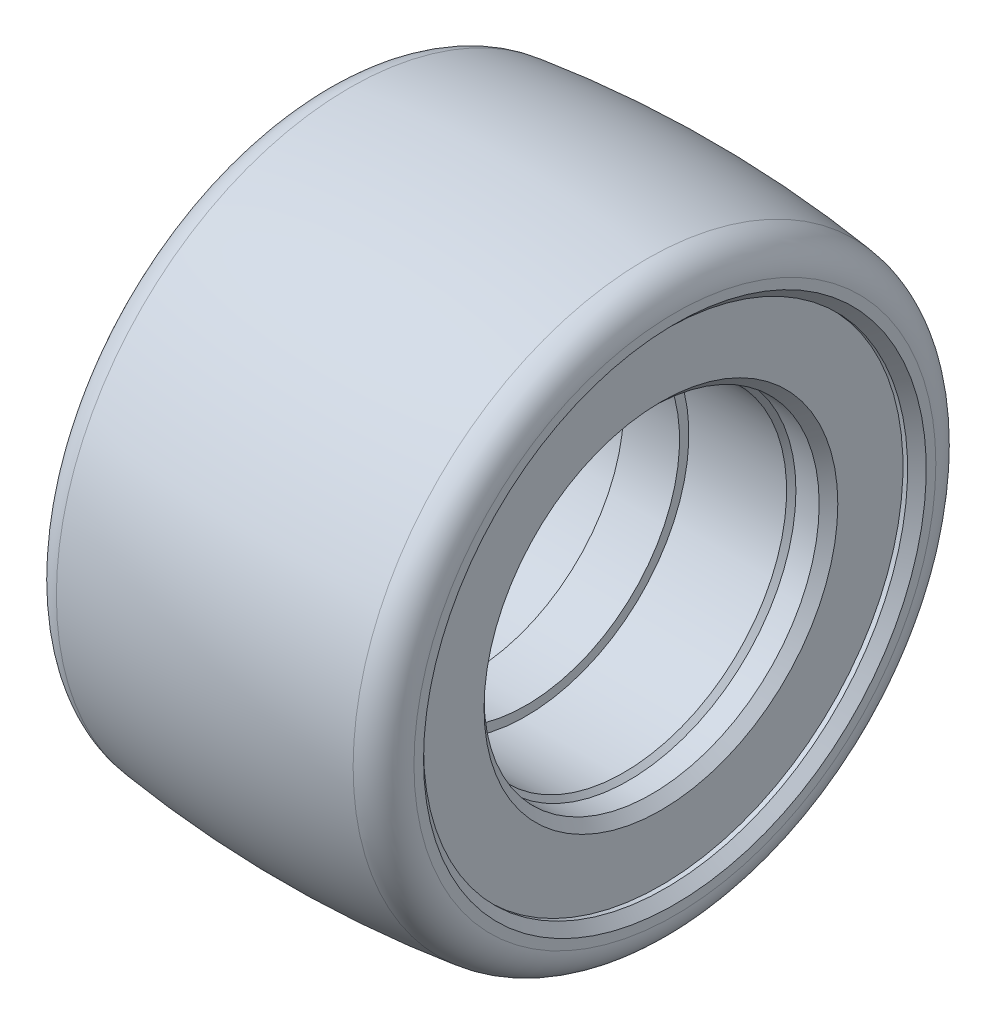
SolidWorks part; units mm, degrees
ref_plane "Front Plane" through (0, 0, 0) normal (0, 0, 1) x (1, 0, 0)
ref_plane "Top Plane" through (0, 0, 0) normal (0, 1, 0) x (1, 0, 0)
ref_plane "Right Plane" through (0, 0, 0) normal (1, 0, 0) x (0, 0, -1)
ref_axis "Axis_X" through (-17.6, 0, 0) along (1, 0, 0)
ref_axis "Axis_Y" through (0, 41.25, 0) along (0, -1, 0)
ref_axis "Axis_Z" through (0, 0, -41.25) along (0, 0, 1)
sketch "Sketch1" plane through (0, 0, 0) normal (0, 0, 1) x (1, 0, 0)
  line L0 (-14, 0) -> (14, 0) construction
  line L2 (-14, 17.5) -> (-3, 17.5)
  line L4 (-19, 32.5) -> (19, 32.5)
  line L5 (0, 0) -> (0, 32.5) construction
  line L8 (-14, 0) -> (14, 0) construction
  line L9 (-3, 17.5) -> (-3, 16.5)
  line L10 (-3, 16.5) -> (3, 16.5)
  line L11 (3, 16.5) -> (3, 17.5)
  line L12 (14, 17.5) -> (14, 18)
  line L13 (14, 18) -> (17.5, 18)
  line L14 (-14, 17.5) -> (-14, 18)
  line L15 (-19, 26) -> (-19, 32.5)
  line L16 (19, 26) -> (19, 32.5)
  line L17 (-14, 18) -> (-17.5, 18)
  line L18 (17.5, 18) -> (17.5, 26)
  line L19 (17.5, 26) -> (19, 26)
  line L20 (3, 17.5) -> (14, 17.5)
  line L21 (-17.5, 18) -> (-17.5, 26)
  line L22 (-17.5, 26) -> (-19, 26)
  dimension "B" = 38
  dimension "D" = 65
  dimension "FIX_1" = 1.5
  dimension "FIX_2" = 1
  dimension "FIX_3" = 1.5
  dimension "FIX_4" = 6
  dimension "FIX_5" = 33
  dimension "FIX_6" = 52
  dimension "FIX_7" = 28
revolve "Revolve1" add sketch "Sketch1" angle 360 about axis through (-17.6, 0, 0) along (1, 0, 0) region at (0, 25.1101, 0)
sketch "Sketch2" plane through (0, 0, 0) normal (0, 0, 1) x (1, 0, 0)
  line L0 (0, 0) -> (19, 0) construction
  line L1 (19, -32.5) -> (19, 32.5) construction
  line L2 (-19, 32.5) -> (-19, -32.5) construction
  line L5 (19, 32.5) -> (-19, 32.5) construction
  line L7 (-19, 46.0764) -> (19, 46.0764)
  line L8 (19, 46.0764) -> (19, 31.0764)
  line L10 (-19, 31.0764) -> (-19, 46.0764)
  arc A0 (-19, 31.0764) -> (19, 31.0764) centre (0, -95) cw
  dimension "FIX_9" = 127.5
  dimension "FIX_10" = 15
revolve "Cut-Revolve1" cut sketch "Sketch2" angle 360 about axis through (-17.6, 0, 0) along (1, 0, 0)
chamfer "Chamfer1" distance 1 angle 45 4 edges at (17.5, 0, 18) (19, 0, 26) (-17.5, 0, 18) (-19, 0, 26)
chamfer "Chamfer2" distance 0.5 angle 45 2 edges at (14, 0, 17.5) (-14, 0, 17.5)
fillet "Fillet1" radius 3.5 2 edges at (-19, 0, 31.0764) (19, 0, 31.0764)
